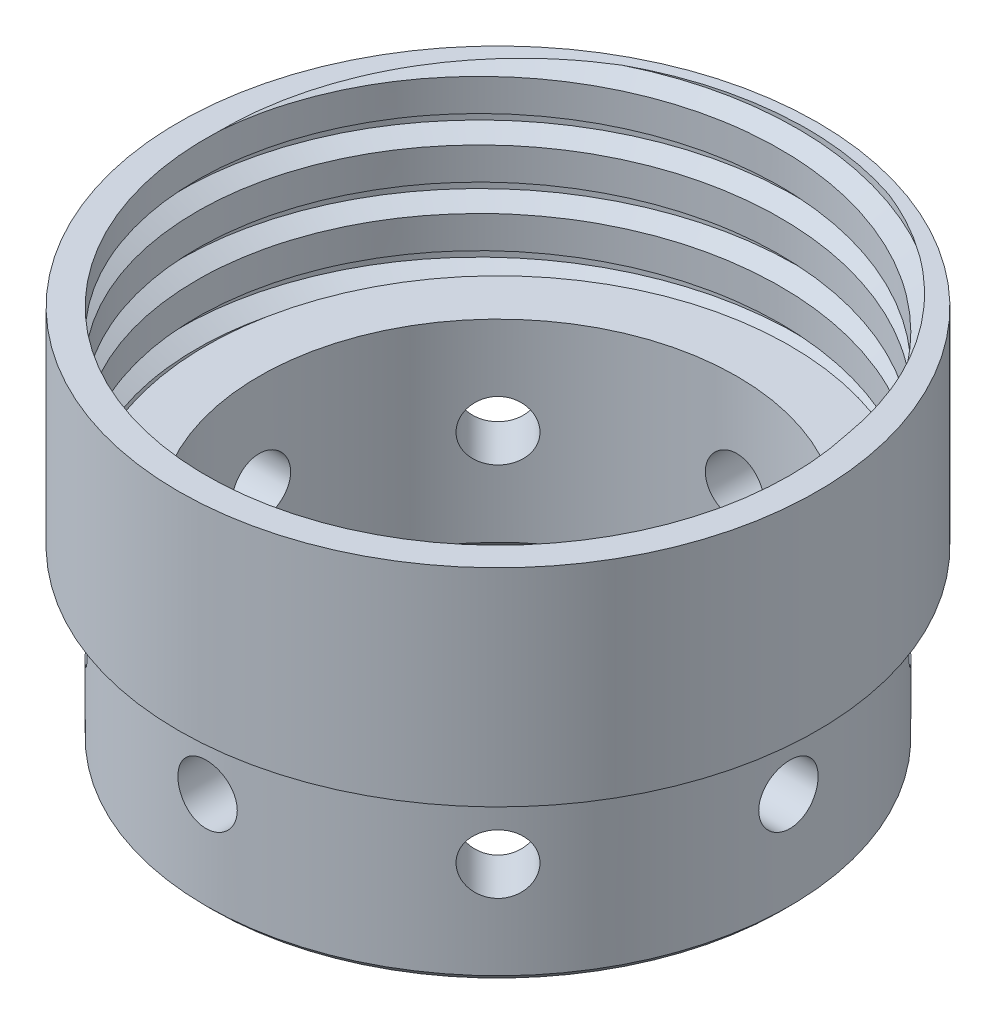
SolidWorks part; units mm, degrees
ref_plane "Front Plane" through (0, 0, 0) normal (0, 0, 1) x (1, 0, 0)
ref_plane "Top Plane" through (0, 0, 0) normal (0, 1, 0) x (1, 0, 0)
ref_plane "Right Plane" through (0, 0, 0) normal (1, 0, 0) x (0, 0, -1)
sketch "Sketch294" plane through (0, 0, 0) normal (0, 0, 1) x (1, 0, 0)
  line L0 (0, 0) -> (-46.28, 0) construction
  line L1 (-46.28, 0) -> (-46.28, -30)
  line L2 (-46.28, -30) -> (-42.28, -30)
  line L3 (-42.28, -30) -> (-42.28, -55)
  line L4 (-42.28, -55) -> (-34.6, -55)
  line L5 (-34.6, -55) -> (-34.6, -26)
  line L6 (-34.6, -26) -> (-42.28, -26)
  line L7 (-42.28, -26) -> (-42.28, 0)
  line L8 (-42.28, 0) -> (-46.28, 0)
  line L9 (0, 0) -> (0, 42.28) construction
  dimension "D1" = 4
  dimension "D2" = 30
  dimension "D3" = 25
  dimension "D4" = 42.28
  dimension "D5" = 4
  dimension "D6" = 34.6
revolve "Revolve1" add sketch "Sketch294" angle 360 about L9
thread "Rosca1" pitch 4.5 start angle 0, offset 4, length 30, pitch 8.6, diameter 84.56
ref_plane "Plano2" through (-42.28, 4, 0) normal (0, 0, 1) x (-1, 0, 0)
sketch "Perfil de rosca2" plane through (-42.28, 4, 0) normal (0, 0, 1) x (-1, 0, 0)
  line L0 (0, 0) -> (0, 4.5) construction
  line L11 (0, 3.9375) -> (0, 0)
  line L12 (0, 0) -> (2.4357, 1.4063)
  line L13 (2.4357, 1.4063) -> (2.4357, 2.5313)
  line L15 (2.4357, 2.5313) -> (0, 3.9375)
  line L17 (2.4357, 1.9688) -> (0, 1.9688) construction
  point P3 (0, 0)
  dimension "Pitch" = 4.5
  dimension "Profile_Angle" = 60
  dimension "Profile_Land" = 1.125
  dimension "Profile_Height" = 2.4357
ref_plane "Plane2" through (0, 0, 38.15) normal (0, 0, 1) x (1, 0, 0)
ref_plane "Plane3" through (38.15, 0, 0) normal (1, 0, 0) x (0, 0, -1)
ref_plane "Plane4" through (26.9761, 0, 26.9761) normal (0.7071, 0, 0.7071) x (0, -1, 0)
ref_plane "Plane5" through (26.9761, 0, -26.9761) normal (0.7071, 0, -0.7071) x (-0.7071, 0, -0.7071)
sketch "Sketch303" plane through (0, 0, 38.15) normal (0, 0, 1) x (1, 0, 0)
  line L0 (0, -40) -> (0, -55) construction
  line L2 (-42.28, -55) -> (42.28, -55) construction
  circle A0 centre (0, -40) radius 4.3
  dimension "D1" = 8.6
  dimension "D2" = 15
extrude "Cut-Extrude1" cut sketch "Sketch303" against normal through all both and the other way through all contours A0
sketch "Sketch304" plane through (38.15, 0, 0) normal (1, 0, 0) x (0, 0, -1)
  line L0 (0, -40) -> (0, -55) construction
  line L1 (-42.28, -55) -> (42.28, -55) construction
  circle A0 centre (0, -40) radius 4.3
  dimension "D1" = 8.6
  dimension "D2" = 15
extrude "Cut-Extrude2" cut sketch "Sketch304" against normal through all both and the other way through all contours A0
sketch "Sketch306" plane through (26.9761, 0, 26.9761) normal (0.7071, 0, 0.7071) x (0, -1, 0)
  line L0 (29.9999, 0) -> (40, 0) construction
  line L1 (29.9998, -37.2423) -> (30, 42.28) construction
  line L2 (40, 0) -> (55, 0) construction
  line L3 (55, -42.28) -> (55, 42.28) construction
  circle A0 centre (40, 0) radius 4.3
  dimension "D2" = 15
extrude "Cut-Extrude3" cut sketch "Sketch306" against normal through all both and the other way through all
sketch "Sketch307" plane through (26.9761, 0, -26.9761) normal (0.7071, 0, -0.7071) x (-0.7071, 0, -0.7071)
  line L0 (0, -40) -> (0, -55) construction
  line L2 (0, 0) -> (0, -40) construction
  line L3 (-42.28, -55) -> (42.28, -55) construction
  circle A0 centre (0, -40) radius 4.3
  dimension "D1" = 8.6
  dimension "D2" = 15
extrude "Cut-Extrude4" cut sketch "Sketch307" against normal through all both and the other way through all
chamfer "Chaflán2" distance 1 angle 45 2 edges at (0, -55, -34.6) (0, -55, -42.28)
